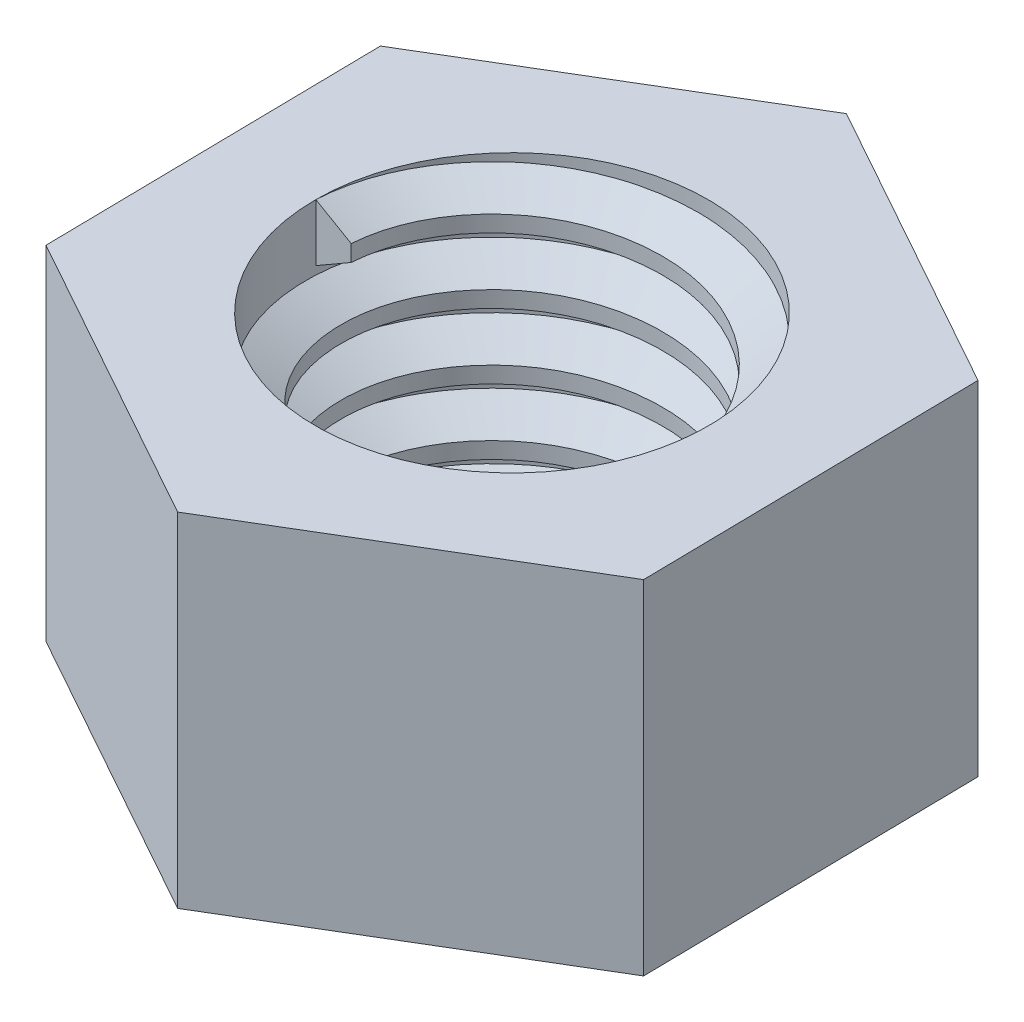
SolidWorks part; units mm, degrees
ref_plane "Front Plane" through (0, 0, 0) normal (0, 0, 1) x (1, 0, 0)
ref_plane "Top Plane" through (0, 0, 0) normal (0, 1, 0) x (1, 0, 0)
ref_plane "Right Plane" through (0, 0, 0) normal (1, 0, 0) x (0, 0, -1)
sketch "Sketch1" plane through (0, 0, 0) normal (0, 1, 0) x (1, 0, 0)
  line L1 (7.0781, 4.2361) -> (-0.1296, 8.2479)
  line L2 (-0.1296, 8.2479) -> (-7.2076, 4.0117)
  line L3 (-7.2076, 4.0117) -> (-7.0781, -4.2361)
  line L4 (-7.0781, -4.2361) -> (0.1296, -8.2479)
  line L5 (0.1296, -8.2479) -> (7.2076, -4.0117)
  line L6 (7.2076, -4.0117) -> (7.0781, 4.2361)
  circle A0 centre (0, 0) radius 7.1438 construction
  circle A1 centre (0, 0) radius 4.7625
  dimension "D2" = 9.525
  dimension "D1" = 14.2875
extrude "Boss-Extrude1" add sketch "Sketch1" along normal blind 8.3344
thread "Thread1" pitch 1.5875 method extrude profile "Thread Profile1" start angle 0, offset 0, length 0, pitch 1.5875, diameter 9.525
ref_plane "Plane1" through (-4.7625, 8.3344, 0) normal (0, 0, 1) x (-1, 0, 0)
sketch "Thread Profile1" plane through (-4.7625, 8.3344, 0) normal (0, 0, 1) x (-1, 0, 0)
  line L0 (0, 0) -> (0, 1.5875) construction
  line L11 (0, 0) -> (0, 1.3891)
  line L12 (0, 1.3891) -> (-0.8593, 0.893)
  line L13 (-0.8593, 0.893) -> (-0.8593, 0.4961)
  line L15 (-0.8593, 0.4961) -> (0, 0)
  line L17 (-0.8593, 0.6945) -> (0, 0.6945) construction
  point P2 (0, 0)
  dimension "Pitch" = 1.5875
  dimension "Profile_Angle" = 60
  dimension "Profile_Land" = 0.3969
  dimension "Profile_Height" = 0.8593
sketch "Sketch4" plane through (0, 0, 0) normal (0, -1, 0) x (1, 0, 0)
  circle A0 centre (0, 0) radius 12.5674
extrude "Cut-Extrude1" cut sketch "Sketch4" along normal blind 16.2719
